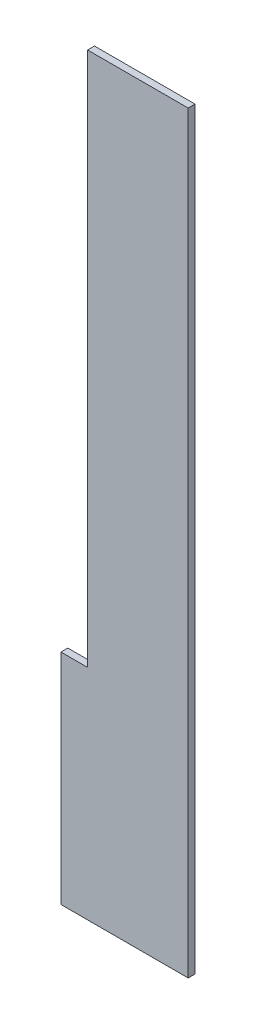
SolidWorks part; units mm, degrees
ref_plane "Ön Düzlem" through (0, 0, 0) normal (0, 0, 1) x (1, 0, 0)
ref_plane "Üst Düzlem" through (0, 0, 0) normal (0, 1, 0) x (1, 0, 0)
ref_plane "Sağ Düzlem" through (0, 0, 0) normal (1, 0, 0) x (0, 0, -1)
sketch "Çizim1" plane through (0, 0, 0) normal (0, 0, 1) x (1, 0, 0)
  line L0 (0, 0) -> (0, -3465)
  line L1 (0, -3465) -> (-660, -3465)
  line L2 (-660, -3465) -> (-660, -6005)
  line L3 (-660, -6005) -> (1360, -6005)
  line L4 (1360, -6005) -> (1360, 0)
  line L5 (1360, 0) -> (0, 0)
  dimension "D1" = 2540
  dimension "D2" = 660
  dimension "D3" = 1360
  dimension "D4" = 3465
  dimension "D5" = 6005
  dimension "D6" = 2020
base flange "Taban-Flanş1" sketch "Çizim1" thickness 40 reverse thickness direction no parameters "D1"=10
sketch "Çizim2" plane through (0, 0, 0) normal (0, 0, 1) x (1, 0, 0)
  line L0 (1360, -6005) -> (1360, 0) construction
  line L1 (0, 0) -> (1360, 0)
  line L2 (0, 0) -> (0, -355)
  line L3 (0, -355) -> (1360, -355)
  line L4 (1360, 0) -> (1360, -355)
  line L5 (0, -3465) -> (-660, -3465) construction
  dimension "D1" = 3110
  dimension "D2" = 355
  dimension "D3" = 1360
extrude "Kes-Ekstrüzyon1" cut sketch "Çizim2" against normal through all both and the other way through all
sketch "Çizim3" plane through (0, 0, 0) normal (0, 0, 1) x (1, 0, 0)
  line L0 (0, -355) -> (1360, -355) construction
  line L1 (0, -3465) -> (365, -3465)
  line L2 (0, -3465) -> (0, -355)
  line L3 (0, -355) -> (365, -355)
  line L4 (365, -3465) -> (365, -355)
  line L5 (-660, -3465) -> (-660, -6005) construction
  line L6 (1360, -6005) -> (1360, -355) construction
  line L7 (-660, -6005) -> (1360, -6005) construction
  line L8 (1360, -355) -> (1355, -355)
  line L9 (1360, -355) -> (1360, -6005)
  line L10 (1360, -6005) -> (1355, -6005)
  line L11 (1355, -355) -> (1355, -6005)
  dimension "D1" = 365
  dimension "D2" = 1025
  dimension "D3" = 3110
  dimension "D4" = 995
  dimension "D5" = 990
extrude "Kes-Ekstrüzyon2" cut sketch "Çizim3" against normal through all both and the other way through all
sketch "Çizim4" plane through (0, 0, 0) normal (0, 0, 1) x (1, 0, 0)
  line L0 (365, -355) -> (1355, -355) construction
  line L1 (770, -355) -> (365, -355)
  line L2 (770, -355) -> (770, -3465)
  line L3 (770, -3465) -> (365, -3465)
  line L4 (365, -355) -> (365, -3465)
  line L5 (1355, -355) -> (1355, -6005) construction
  line L6 (-660, -3465) -> (-660, -6005) construction
  dimension "D1" = 585
  dimension "D2" = 3110
  dimension "D3" = 1430
extrude "Kes-Ekstrüzyon3" cut sketch "Çizim4" against normal through all both and the other way through all
sketch "Çizim5" plane through (0, 0, 0) normal (0, 0, 1) x (1, 0, 0)
  line L0 (615, -3465) -> (615, -4737)
  line L1 (770, -3465) -> (-660, -3465) construction
  line L2 (615, -4737) -> (1355, -4737)
  line L3 (1355, -355) -> (1355, -6005) construction
  line L4 (-660, -3465) -> (-660, -6005) construction
  line L5 (-660, -6005) -> (1355, -6005) construction
  line L6 (770, -3465) -> (770, -355) construction
  line L7 (615, -3465) -> (-660, -3465)
  line L8 (-660, -3465) -> (-660, -6005)
  line L9 (-660, -6005) -> (1355, -6005)
  line L10 (1355, -6005) -> (1355, -4737)
  dimension "D1" = 1275
  dimension "D2" = 1268
  dimension "D3" = 155
  dimension "D4" = 740
  dimension "D5" = 1272
  dimension "D6" = 2540
extrude "Kes-Ekstrüzyon4" cut sketch "Çizim5" against normal through all both and the other way through all
sketch "Büküm-Çizgileri1" [suppressed] plane through (0, 0, 0) normal (0, 1, 0) x (1, 0, 0)
sketch "Sınırlandırma-Kutusu1" [suppressed] plane through (0, 0, 0) normal (0, 1, 0) x (1, 0, 0)
sheet metal parameters "Sac-Levha1" thickness 40 parameters "D1"=10
flat pattern "Düz-Çoğaltma1" [suppressed]
sketch "Büküm-Çizgileri2" plane through (0, 0, 0) normal (0, 1, 0) x (1, 0, 0)
sketch3d "Sınırlandırma-Kutusu2" [suppressed]
  line L0 (1360, 0, 0) -> (1360, -6005, 0) construction
  line L1 (-660, 0, 0) -> (-660, -6005, 0) construction
  line L2 (1360, 0, 0) -> (-660, 0, 0) construction
  line L3 (1360, -6005, 0) -> (-660, -6005, 0) construction
sheet metal parameters "Sac-Levha2" thickness 40 parameters "D1"=10
flat pattern "Düz-Çoğaltma1"
sketch "Büküm-Çizgileri2" plane through (0, 0, 0) normal (0, 1, 0) x (1, 0, 0)
sketch3d "Sınırlandırma-Kutusu2" [suppressed]
  line L0 (1360, -355, 0) -> (1360, -6005, 0) construction
  line L1 (-660, -355, 0) -> (-660, -6005, 0) construction
  line L2 (1360, -355, 0) -> (-660, -355, 0) construction
  line L3 (1360, -6005, 0) -> (-660, -6005, 0) construction
sheet metal parameters "Sac-Levha3" thickness 40 parameters "D1"=10
flat pattern "Düz-Çoğaltma1"
sketch "Büküm-Çizgileri2" plane through (0, 0, 0) normal (0, 1, 0) x (1, 0, 0)
sketch3d "Sınırlandırma-Kutusu2" [suppressed]
  line L0 (1355, -355, 0) -> (1355, -6005, 0) construction
  line L1 (-660, -355, 0) -> (-660, -6005, 0) construction
  line L2 (1355, -355, 0) -> (-660, -355, 0) construction
  line L3 (1355, -6005, 0) -> (-660, -6005, 0) construction
sheet metal parameters "Sac-Levha4" thickness 40 parameters "D1"=10
flat pattern "Düz-Çoğaltma1"
sketch "Büküm-Çizgileri2" plane through (0, 0, 0) normal (0, 1, 0) x (1, 0, 0)
sketch3d "Sınırlandırma-Kutusu2" [suppressed]
  line L0 (1355, -355, 0) -> (1355, -6005, 0) construction
  line L1 (-660, -355, 0) -> (-660, -6005, 0) construction
  line L2 (1355, -355, 0) -> (-660, -355, 0) construction
  line L3 (1355, -6005, 0) -> (-660, -6005, 0) construction
sheet metal parameters "Sac-Levha5" thickness 40 parameters "D1"=10
flat pattern "Düz-Çoğaltma1"
sketch "Büküm-Çizgileri2" plane through (0, 0, 0) normal (0, 1, 0) x (1, 0, 0)
sketch3d "Sınırlandırma-Kutusu2" [suppressed]
  line L0 (1355, -355, 0) -> (1355, -4737, 0) construction
  line L1 (615, -355, 0) -> (615, -4737, 0) construction
  line L2 (1355, -355, 0) -> (615, -355, 0) construction
  line L3 (1355, -4737, 0) -> (615, -4737, 0) construction
